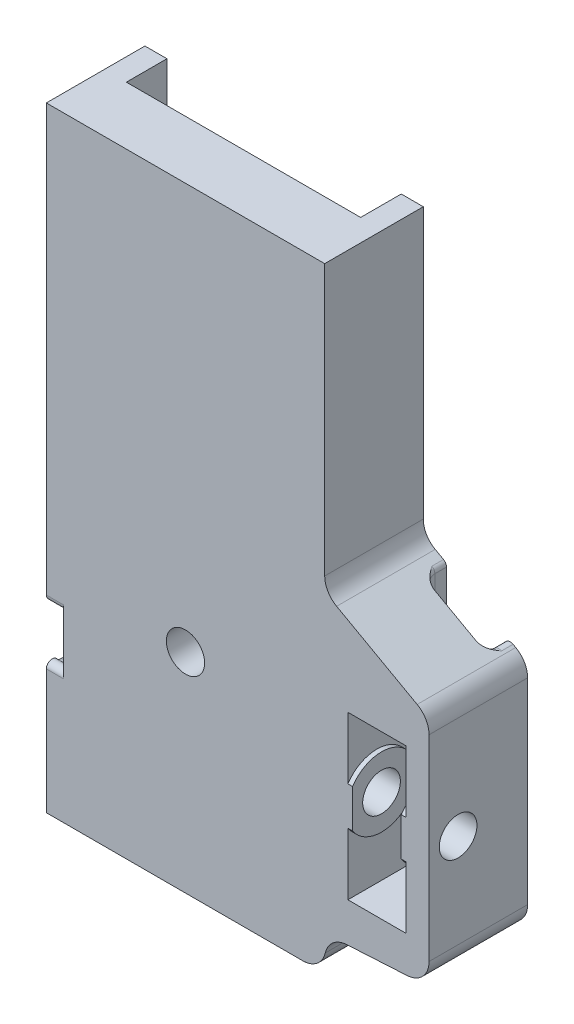
SolidWorks part; units mm, degrees
material "ABS"
ref_plane "前视基准面" through (0, 0, 0) normal (0, 0, 1) x (1, 0, 0)
ref_plane "上视基准面" through (0, 0, 0) normal (0, 1, 0) x (1, 0, 0)
ref_plane "右视基准面" through (0, 0, 0) normal (1, 0, 0) x (0, 0, -1)
other "Configuration Table"
sketch "草图1" plane through (0, 0, 0) normal (0, 0, 1) x (1, 0, 0)
  line L0 (0, 0) -> (0, 53)
  line L1 (0, 53) -> (24, 53)
  line L2 (24, 53) -> (24, 28.5)
  line L3 (24, 28.5) -> (33, 23.5)
  line L4 (33, 23.5) -> (33, 3.5)
  line L5 (33, 3.5) -> (24, 3)
  line L6 (24, 3) -> (24, 0)
  line L7 (24, 0) -> (0, 0)
  line L9 (26, 20.5) -> (31, 20.5)
  line L10 (26, 20.5) -> (26, 6.5)
  line L11 (26, 6.5) -> (31, 6.5)
  line L12 (31, 20.5) -> (31, 6.5)
  circle A0 centre (12, 18) radius 1.65
  dimension "D12" = 3.3
  dimension "D13" = 12
  dimension "D14" = 18
  dimension "D1" = 53
  dimension "D2" = 24
  dimension "D3" = 9
  dimension "D4" = 3
  dimension "D5" = 20
  dimension "D6" = 24.5
  dimension "D7" = 29.5
  dimension "D8" = 5
  dimension "D9" = 14
  dimension "D10" = 2
  dimension "D11" = 3
extrude "凸台-拉伸1" add sketch "草图1" along normal blind 8.5
sketch "草图2" plane through (0, 53, 0) normal (0, 1, 0) x (1, 0, 0)
  line L0 (24, 0) -> (0, 0) construction
  line L1 (1.9, 0) -> (22.1, 0)
  line L2 (1.9, 0) -> (1.9, -3.5)
  line L3 (1.9, -3.5) -> (22.1, -3.5)
  line L4 (22.1, 0) -> (22.1, -3.5)
  line L5 (0, -8.5) -> (0, 0) construction
  dimension "D1" = 3.5
  dimension "D2" = 1.9
  dimension "D3" = 20.2
extrude "切除-拉伸1" cut sketch "草图2" against normal offset from surface (50.1 mm away) 2.9 up to face at (12, 0, 4.25)
sketch "草图3" plane through (33, 0, 0) normal (1, 0, 0) x (0, 0, -1)
  line L0 (-8.5, 3.5) -> (-8.5, 23.5) construction
  circle A0 centre (-6, 13.5) radius 1.625
  dimension "D1" = 3.25
  dimension "D2" = 2.5
  dimension "D3" = 7
extrude "切除-拉伸2" cut sketch "草图3" against normal through all
sketch "草图5" plane through (26, 0, 0) normal (1, 0, 0) x (0, 0, -1)
  line L0 (-8.5, 20.5) -> (-8.5, 6.5) construction
  line L1 (-8.5, 15.1583) -> (-8.5, 11.8417)
  circle A1 centre (-6, 13.5) radius 1.625
  arc A2 (-8.5, 11.8417) -> (-8.5, 15.1583) centre (-6, 13.5) ccw
  circle A3 centre (-6, 13.5) radius 1.625 construction
  dimension "D1" = 6
extrude "凸台-拉伸2" add sketch "草图5" along normal blind 0.4
sketch "草图6" plane through (31, 0, 0) normal (-1, 0, 0) x (0, 0, 1)
  line L1 (8.5, 11.8417) -> (8.5, 15.1583)
  line L2 (8.5, 11.8417) -> (8.5, 15.1583)
  circle A0 centre (6, 13.5) radius 1.625 construction
  arc A1 (8.5, 15.1583) -> (8.5, 11.8417) centre (6, 13.5) ccw
  arc A2 (8.5, 15.1583) -> (8.5, 11.8417) centre (6, 13.5) ccw
  circle A3 centre (6, 13.5) radius 1.625
  dimension "D1" = 0
extrude "凸台-拉伸3" add sketch "草图6" along normal blind 0.4
fillet "圆角1" radius 2 1 edges at (24, 3, 4.25)
fillet "圆角2" radius 2 4 edges at (24, 0, 4.25) (33, 3.5, 4.25) (33, 23.5, 4.25) (24, 28.5, 4.25)
sketch "草图7" plane through (0, 0, 0) normal (0, 0, -1) x (-1, 0, 0)
  line L0 (-26, 20.5) -> (-26, 6.5) construction
  line L1 (-31, 20.5) -> (-26, 20.5)
  line L2 (-31, 20.5) -> (-31, 31.2611)
  line L3 (-31, 31.2611) -> (-26, 31.2611)
  line L4 (-26, 20.5) -> (-26, 31.2611)
extrude "切除-拉伸3" cut sketch "草图7" against normal blind 2
fillet "圆角3" radius 0.5 2 edges at (31, 24.6111, 1) (26, 27.3889, 1)
fillet "圆角4" radius 1 4 edges at (31.2464, 24.1923, 2) (25.9309, 27.3483, 2) (31, 22.1307, 2) (26, 23.7973, 2)
sketch "草图8" plane through (0, 0, 0) normal (-1, 0, 0) x (0, 0, 1)
  line L1 (2.9689, 13.5) -> (4.4845, 10.875)
  line L2 (4.4845, 10.875) -> (7.5155, 10.875)
  line L3 (7.5155, 10.875) -> (9.0311, 13.5)
  line L4 (9.0311, 13.5) -> (7.5155, 16.125)
  line L5 (7.5155, 16.125) -> (4.4845, 16.125)
  line L6 (4.4845, 16.125) -> (2.9689, 13.5)
  circle A0 centre (6, 13.5) radius 2.625 construction
  dimension "D1" = 5.25
extrude "切除-拉伸4" cut sketch "草图8" against normal blind 1.5
fillet "圆角5" radius 0.5 5 edges at (0.75, 10.875, 7.5155) (0.75, 10.875, 4.4845) (0.75, 13.5, 2.9689) (0.75, 16.125, 4.4845) (0.75, 16.125, 7.5155)
fillet "圆角6" radius 0.5 2 edges at (0.75, 12.5801, 8.5) (0.75, 14.4199, 8.5)
